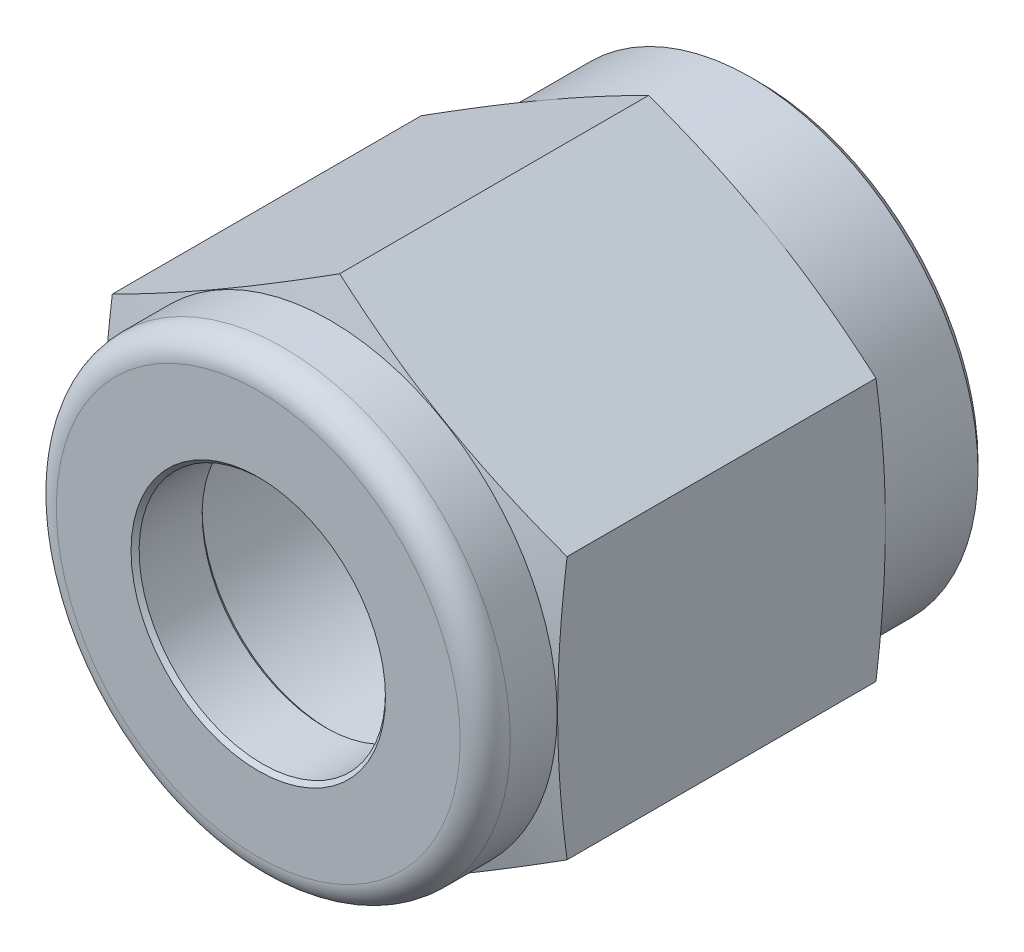
SolidWorks part; units mm, degrees
material "2024 Alloy"
ref_plane "Front Plane" through (0, 0, 0) normal (0, 0, 1) x (1, 0, 0)
ref_plane "Top Plane" through (0, 0, 0) normal (0, 1, 0) x (1, 0, 0)
ref_plane "Right Plane" through (0, 0, 0) normal (1, 0, 0) x (0, 0, -1)
sketch "Sketch0" plane through (0, 0, 0) normal (1, 0, 0) x (0, 0, -1)
  line L0 (0, 0) -> (-15.748, 0) construction
  line L4 (-15.748, 7.1501) -> (-15.748, -7.1501) construction
  line L5 (-15.748, 7.1374) -> (-15.748, -7.1374) construction
  line L6 (-15.748, 3.8735) -> (-15.748, -3.8735) construction
  line L7 (0, 5.5562) -> (0, -5.5562) construction
  line L8 (0, -5.5626) -> (0, 5.5626) construction
  line L9 (0, -5.5626) -> (-1.27, -5.5626) construction
  point P16 (-13.5128, 0)
  point P20 (-12.7, 0)
  point P22 (-9.652, 0)
  point P34 (-3.175, 0)
  point P35 (-13.4874, 0)
  dimension "P" = 14.3002
  dimension "M" = 15.748
  dimension "L" = 13.5128
  dimension "S" = 12.7
  dimension "Q" = 9.652
  dimension "A" = 7.747
  dimension "C" = 14.2748
  dimension "T" = 11.1125
  dimension "B" = 3.175
  dimension "J" = 10.3124
  dimension "H" = 11.1252
  dimension "Pitch" = 1.27
sketch "Sketch1" plane through (0, 0, 0) normal (0, 0, 1) x (1, 0, 0)
  line L1 (0, 8.2562) -> (-7.1501, 4.1281)
  line L2 (-7.1501, 4.1281) -> (-7.1501, -4.1281)
  line L3 (-7.1501, -4.1281) -> (0, -8.2562)
  line L4 (0, -8.2562) -> (7.1501, -4.1281)
  line L5 (7.1501, -4.1281) -> (7.1501, 4.1281)
  line L6 (7.1501, 4.1281) -> (0, 8.2562)
  circle A0 centre (0, 0) radius 7.1501 construction
extrude "Boss-Extrude1" add sketch "Sketch1" along normal up to vertex (15.748 mm away) up to point (0, 0, 15.748)
sketch "Sketch2" plane through (0, 0, 0) normal (1, 0, 0) x (0, 0, -1)
  line L0 (-15.748, 9.375) -> (-15.748, 7.1374)
  line L1 (-15.748, 7.1374) -> (-13.4874, 7.1374)
  line L2 (-13.4874, 7.1374) -> (-13.1876, 8.2562)
  line L3 (-15.748, 8.2562) -> (0, 8.2562) construction
  line L4 (-13.1876, 8.2562) -> (-3.4748, 8.2562)
  line L5 (-3.4748, 8.2562) -> (-3.175, 7.1374)
  line L6 (-3.175, 7.1374) -> (-13.4874, 7.1374) construction
  line L7 (-3.175, 7.1374) -> (0, 7.1374)
  line L8 (0, 7.1374) -> (0, 9.375)
  line L9 (-15.748, 9.375) -> (0, 9.375)
  line L10 (-3.175, 7.1374) -> (-3.175, 0) construction
  line L11 (-13.4874, 7.1374) -> (-13.4874, 0) construction
  line L12 (-15.748, 3.8735) -> (-15.748, 0)
  line L13 (-15.748, 7.1501) -> (-15.748, -7.1501) construction
  line L14 (-15.748, 0) -> (0, 0)
  line L15 (0, 0) -> (0, 4.7829)
  line L16 (-13.5128, 3.8735) -> (-13.5128, 0) construction
  line L17 (-13.5128, 3.8735) -> (-13.5128, 4.5289)
  line L18 (-13.2588, 4.7829) -> (0, 4.7829)
  line L19 (-13.5128, 3.8735) -> (-15.748, 3.8735)
  line L23 (-12.7, 0) -> (-12.7, 4.7829) construction
  arc A0 (-13.5128, 4.5289) -> (-13.2588, 4.7829) centre (-13.2588, 4.5289) cw
  dimension "D3" = 0.254
  dimension "D1" = 15
  dimension "D2" = 15
  dimension "D4" = 0.7733
revolve "Cut-Revolve1" cut sketch "Sketch2" angle 360 about L0
sketch "Sketch3" [suppressed] plane through (0, 0, 0) normal (0, 0, -1) x (-1, 0, 0)
  circle A0 centre (0, 0) radius 4.7829
  circle A1 centre (0, 0) radius 4.7829 construction
  point P3 (0, 4.7829)
fillet "Fillet1" radius 0.7874 1 edges at (0, 7.1374, 15.748)
chamfer "Chamfer1" distance 0.254 angle 45 1 edges at (0, 7.1374, 0)
chamfer "Chamfer2" distance 0.127 angle 45 2 edges at (0, 3.8735, 13.5128) (0, 3.8735, 15.748)
ref_axis "Centre Axis 1" through (0, 0, 25.2505) along (0, 0, -1)
curve "Helix/Spiral1" [suppressed] pitch 1.27 height 13.97 turns 11 parameters "Pitch"=1.27
sketch "Sketch4" [suppressed] plane through (0, 0, 0) normal (1, 0, 0) x (0, 0, -1)
  line L0 (-0.248, 4.3533) -> (1.022, 4.3533) construction
  line L1 (1.022, 4.3533) -> (0.387, 5.4531) construction
  line L2 (0.387, 5.4531) -> (-0.248, 4.3533) construction
  line L3 (0.2877, 5.2813) -> (0.4862, 5.2813) construction
  line L4 (0.387, 4.7829) -> (0.387, 4.3533) construction
  line L5 (0, 4.7829) -> (0.7739, 4.7829) construction
  line L6 (0.387, 5.4531) -> (0.387, 5.2813) construction
  line L7 (0.2877, 5.2813) -> (-0.124, 4.5681)
  line L8 (-0.124, 4.5681) -> (0.8979, 4.5681)
  line L9 (0.8979, 4.5681) -> (0.4862, 5.2813)
  arc A0 (0.4862, 5.2813) -> (0.2877, 5.2813) centre (0.387, 5.224) ccw
  point P6 (0.387, 4.5681)
  dimension "D1" = 1.27
  dimension "D2" = 1.0999
  dimension "D4" = 0.4296
  dimension "D3" = 0.1719
  dimension "D5" = 0.4984
sweep "Cut-Sweep1" [suppressed] cut profiles "Sketch4" path "Helix/Spiral1"
sketch "Sketch5" [suppressed] plane through (0, 0, 0) normal (0, 0, -1) x (-1, 0, 0)
  circle A0 centre (0, 0) radius 5.5626
extrude "Cut-Extrude1" [suppressed] cut sketch "Sketch5" against normal through all draft 45
sketch "Sketch6" [suppressed] plane through (0, 0, 0) normal (1, 0, 0) x (0, 0, -1)
  line L0 (-13.5128, 5.4531) -> (-9.652, 5.4531)
  line L1 (-9.652, 5.4531) -> (-12.7, 4.7829)
  line L2 (-12.7, 4.7829) -> (-13.5128, 4.7829)
  line L3 (-13.5128, 4.7829) -> (-13.5128, 5.4531)
  line L4 (-9.652, 0) -> (-9.652, 5.4531) construction
  line L5 (-12.7, 0) -> (-12.7, 4.7829) construction
  line L7 (-13.5128, 4.7829) -> (-13.5128, 0) construction
  line L8 (-13.2588, 4.7829) -> (0, 4.7829) construction
  line L9 (-9.652, 5.4531) -> (0.387, 5.4531) construction
revolve "Revolve1" [suppressed] add sketch "Sketch6" angle 360 about L0
sketch "SketchX" [suppressed] plane through (0, 0, 0) normal (0, 0, -1) x (-1, 0, 0)
  line L0 (0, 0) -> (-2.7813, 4.8174) construction
  line L1 (0, 8.2562) -> (-7.1501, 4.1281) construction
  circle A0 centre (0, 0) radius 5.5626 construction
equation "\"D3@Helix/Spiral1\"= \"Pitch@Sketch0\" + \"S@Sketch0\""
equation "\"D1@Sketch4\"=\"Pitch@Sketch0\""
equation "\"Pitch@Helix/Spiral1\"=\"Pitch@Sketch0\""
